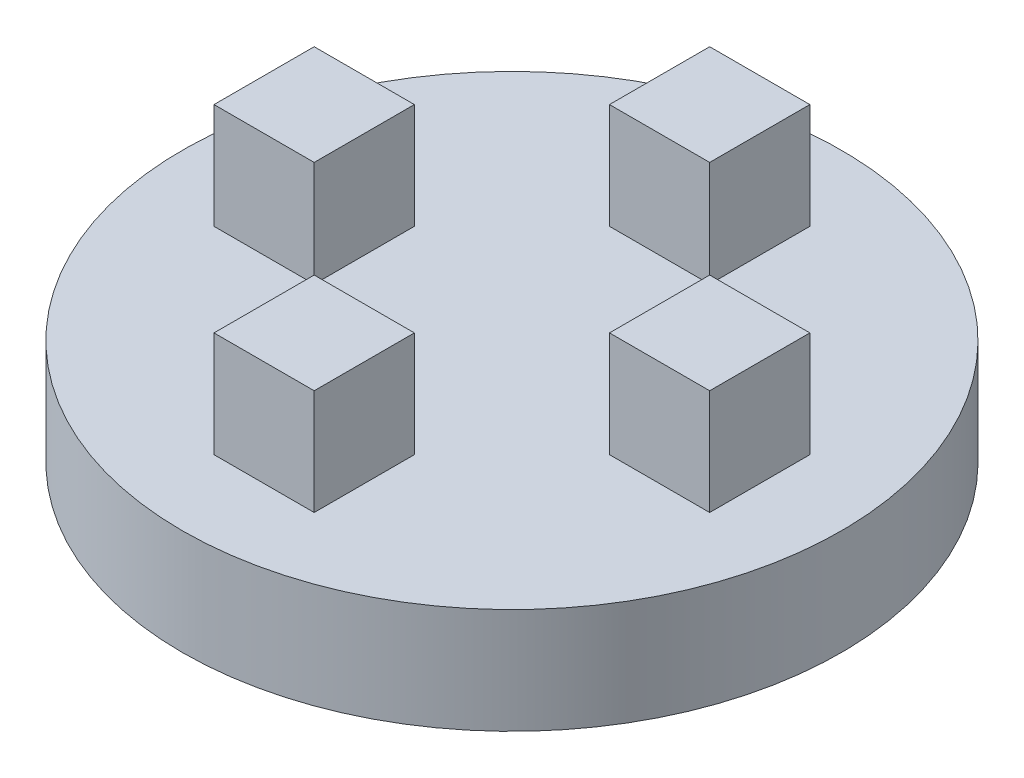
SolidWorks part; units mm, degrees
ref_plane "Front Plane" through (0, 0, 0) normal (0, 0, 1) x (1, 0, 0)
ref_plane "Top Plane" through (0, 0, 0) normal (0, 1, 0) x (1, 0, 0)
ref_plane "Right Plane" through (0, 0, 0) normal (1, 0, 0) x (0, 0, -1)
sketch "Sketch1" plane through (0, 0, 0) normal (0, 1, 0) x (1, 0, 0)
  circle A0 centre (0, 0) radius 12.5
  dimension "D1" = 25
extrude "Boss-Extrude1" add sketch "Sketch1" along normal mid plane 4
sketch "Sketch2" plane through (0, 2, 0) normal (0, 1, 0) x (1, 0, 0)
  line L1 (-2, 9.5) -> (2, 9.5) construction
  line L2 (-2, 9.5) -> (-2, 5.5) construction
  line L3 (-2, 5.5) -> (2, 5.5) construction
  line L4 (2, 9.5) -> (2, 5.5) construction
  line L5 (-1.9, 9.4) -> (-1.9, 5.6)
  line L6 (-1.9, 5.6) -> (1.9, 5.6)
  line L7 (1.9, 9.4) -> (1.9, 5.6)
  line L8 (-1.9, 9.4) -> (1.9, 9.4)
  line L9 (9.4, 1.9) -> (5.6, 1.9)
  line L10 (5.6, 1.9) -> (5.6, -1.9)
  line L11 (9.4, -1.9) -> (5.6, -1.9)
  line L12 (9.4, 1.9) -> (9.4, -1.9)
  line L13 (1.9, -9.4) -> (1.9, -5.6)
  line L14 (1.9, -5.6) -> (-1.9, -5.6)
  line L15 (-1.9, -9.4) -> (-1.9, -5.6)
  line L16 (1.9, -9.4) -> (-1.9, -9.4)
  line L17 (-9.4, -1.9) -> (-5.6, -1.9)
  line L18 (-5.6, -1.9) -> (-5.6, 1.9)
  line L19 (-9.4, 1.9) -> (-5.6, 1.9)
  line L20 (-9.4, -1.9) -> (-9.4, 1.9)
  point P4 (0, 5.5)
  point P25 (0, 0)
  dimension "D1" = 5.5
  dimension "D2" = 4
  dimension "D3" = 4
  dimension "D4" = 0.1
  dimension "D5" = 4
extrude "Boss-Extrude3" add sketch "Sketch2" along normal blind 4
sketch "Sketch3" plane through (0, -2, 0) normal (0, -1, 0) x (1, 0, 0)
  circle A0 centre (0, 0) radius 3.5
  dimension "D1" = 7
extrude "Boss-Extrude4" add sketch "Sketch3" along normal blind 1
sketch "Sketch4" plane through (0, -3, 0) normal (0, -1, 0) x (1, 0, 0)
  line L1 (0, -2.45) -> (2.1218, -1.225)
  line L2 (2.1218, -1.225) -> (2.1218, 1.225)
  line L3 (2.1218, 1.225) -> (0, 2.45)
  line L4 (0, 2.45) -> (-2.1218, 1.225)
  line L5 (-2.1218, 1.225) -> (-2.1218, -1.225)
  line L6 (-2.1218, -1.225) -> (0, -2.45)
  circle A0 centre (0, 0) radius 2.45 construction
  circle A1 centre (0, 0) radius 2.1218 construction
  point P3 (0, -2.5)
  dimension "D1" = 4.9
extrude "Boss-Extrude5" add sketch "Sketch4" along normal blind 5
